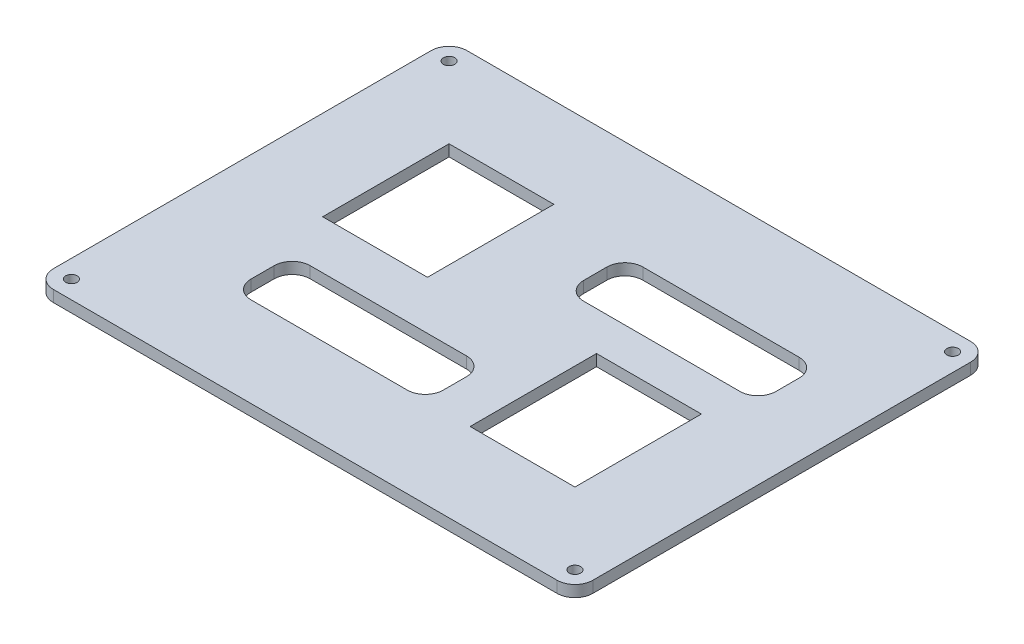
SolidWorks part; units mm, degrees
ref_plane "Front Plane" through (0, 0, 0) normal (0, 0, 1) x (1, 0, 0)
ref_plane "Top Plane" through (0, 0, 0) normal (0, 1, 0) x (1, 0, 0)
ref_plane "Right Plane" through (0, 0, 0) normal (1, 0, 0) x (0, 0, -1)
sketch "Sketch1" plane through (0, 0, 0) normal (0, 1, 0) x (1, 0, 0)
  line L1 (-42.8147, 176.0471) -> (237.1853, 176.0471)
  line L2 (-52.8147, 166.0471) -> (-52.8147, -43.9529)
  line L3 (-42.8147, -53.9529) -> (237.1853, -53.9529)
  line L4 (247.1853, 166.0471) -> (247.1853, -43.9529)
  arc A0 (-52.8147, -43.9529) -> (-42.8147, -53.9529) centre (-42.8147, -43.9529) ccw
  arc A1 (237.1853, -53.9529) -> (247.1853, -43.9529) centre (237.1853, -43.9529) ccw
  arc A2 (237.1853, 176.0471) -> (247.1853, 166.0471) centre (237.1853, 166.0471) cw
  arc A3 (-42.8147, 176.0471) -> (-52.8147, 166.0471) centre (-42.8147, 166.0471) ccw
  circle A4 centre (-42.8147, 166.0471) radius 3.175
  circle A5 centre (237.1853, 166.0471) radius 3.175
  circle A6 centre (237.1853, -43.9529) radius 3.175
  circle A7 centre (-42.8147, -43.9529) radius 3.175
  dimension "D1" = 10
  dimension "D4" = 6.35
  dimension "D2" = 230
  dimension "D3" = 300
extrude "Boss-Extrude1" add sketch "Sketch1" along normal blind 6.35
sketch "Sketch2" plane through (0, 0, 0) normal (0, -1, 0) x (1, 0, 0)
  line L12 (197.3353, -66.1971) -> (139.0353, -66.1971)
  line L13 (197.3353, -66.1971) -> (197.3353, 4.1029)
  line L14 (247.1853, -61.0471) -> (-52.8147, -61.0471) construction
  line L15 (247.1853, 43.9529) -> (247.1853, -166.0471) construction
  line L16 (-52.8147, -166.0471) -> (-52.8147, 43.9529) construction
  line L21 (97.1853, -61.0471) -> (97.1853, -176.0471) construction
  line L22 (237.1853, -176.0471) -> (-42.8147, -176.0471) construction
  line L23 (-2.9647, -55.8971) -> (55.3353, -55.8971)
  line L24 (-2.9647, -55.8971) -> (-2.9647, -126.1971)
  line L25 (-2.9647, -126.1971) -> (55.3353, -126.1971)
  line L26 (55.3353, -55.8971) -> (55.3353, -126.1971)
  line L28 (54.8353, -79.3971) -> (54.8353, -114.6971) construction
  line L29 (-2.4647, -114.6971) -> (-2.4647, -79.3971) construction
  line L30 (43.8353, -125.6971) -> (8.5353, -125.6971) construction
  line L31 (197.3353, 4.1029) -> (139.0353, 4.1029)
  line L32 (33.4082, -56.3971) -> (18.9625, -56.3971) construction
  line L33 (139.0353, -66.1971) -> (139.0353, 4.1029)
  dimension "D1" = 0.5
  dimension "D2" = 0.5
  dimension "D3" = 0.5
  dimension "D4" = 0.5
extrude "Cut-Extrude1" cut sketch "Sketch2" against normal up to surface (6.35 mm away) up to face at (237.1853, 6.35, 47.1279)
sketch "Sketch3" plane through (0, 0, 0) normal (0, -1, 0) x (1, 0, 0)
  line L0 (17.1075, -28.9007) -> (104.0414, -28.9007)
  line L1 (110.2512, -120.7454) -> (197.1851, -120.7454)
  line L2 (100.2512, -110.7454) -> (100.2512, -97.8165)
  line L3 (110.2512, -87.8165) -> (197.1851, -87.8165)
  line L4 (207.1851, -110.7454) -> (207.1851, -97.8165)
  line L5 (7.1075, -18.9007) -> (7.1075, -5.9718)
  line L6 (17.1075, 4.0282) -> (104.0414, 4.0282)
  line L7 (114.0414, -18.9007) -> (114.0414, -5.9718)
  arc A0 (100.2512, -97.8165) -> (110.2512, -87.8165) centre (110.2512, -97.8165) cw
  arc A1 (197.1851, -87.8165) -> (207.1851, -97.8165) centre (197.1851, -97.8165) cw
  arc A2 (197.1851, -120.7454) -> (207.1851, -110.7454) centre (197.1851, -110.7454) ccw
  arc A3 (110.2512, -120.7454) -> (100.2512, -110.7454) centre (110.2512, -110.7454) cw
  arc A4 (7.1075, -5.9718) -> (17.1075, 4.0282) centre (17.1075, -5.9718) cw
  arc A5 (104.0414, 4.0282) -> (114.0414, -5.9718) centre (104.0414, -5.9718) cw
  arc A6 (104.0414, -28.9007) -> (114.0414, -18.9007) centre (104.0414, -18.9007) ccw
  arc A7 (17.1075, -28.9007) -> (7.1075, -18.9007) centre (17.1075, -18.9007) cw
  dimension "D1" = 10
  dimension "D2" = 10
extrude "Cut-Extrude2" cut sketch "Sketch3" against normal up to surface (6.35 mm away) up to face at (168.1853, 6.35, -31.0471)
